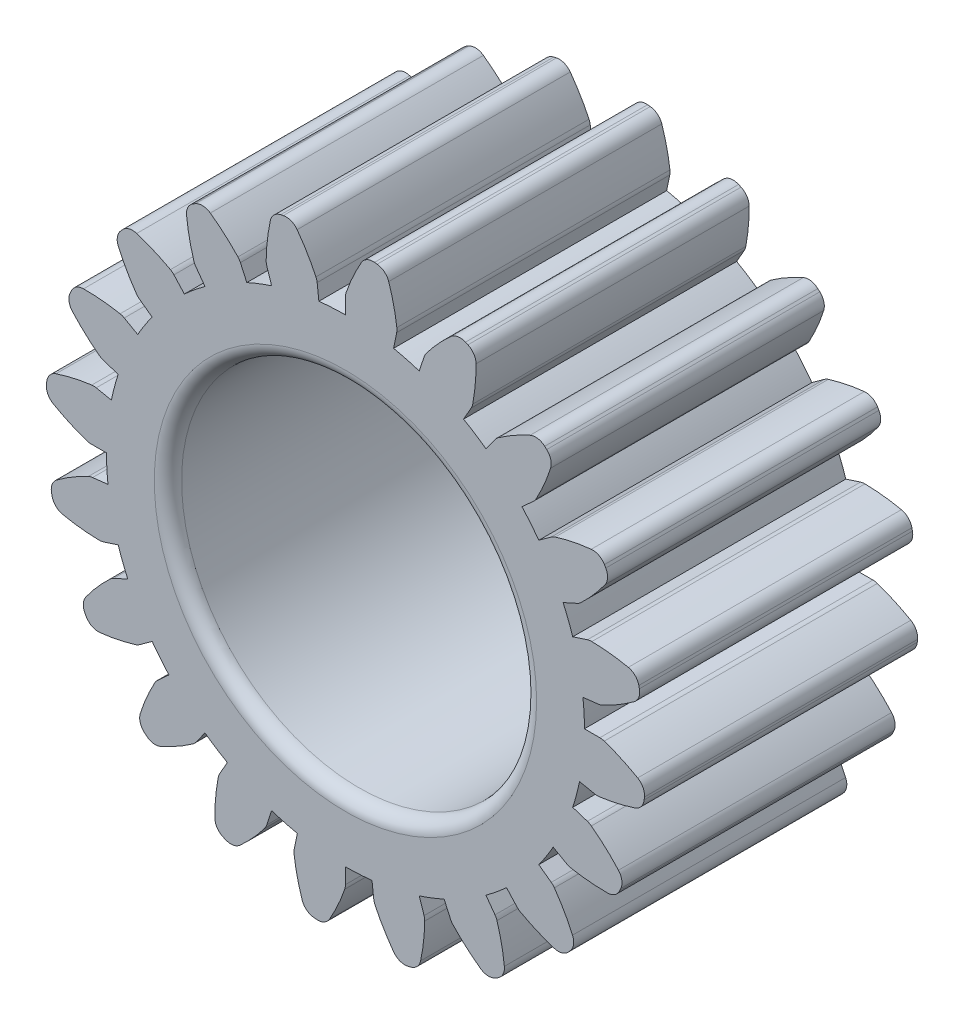
SolidWorks part; units mm, degrees
ref_plane "Front Plane" through (0, 0, 0) normal (1, 0, 0) x (0, 1, 0)
ref_plane "Top Plane" through (0, 0, 0) normal (0, 0, 1) x (0, 1, 0)
ref_plane "Right Plane" through (0, 0, 0) normal (0, 1, 0) x (-1, 0, 0)
sketch "Sketch1" plane through (0, 0, 0) normal (0, 0, 1) x (0, 1, 0)
  line L1 (0, 0) -> (0, 9.3969) construction
  line L2 (0, 0) -> (3.596, 8.6816) construction
  line L3 (0, 0) -> (6.6446, 6.6446) construction
  line L4 (0, 0) -> (8.6816, 3.596) construction
  line L5 (0, 0) -> (9.3969, 0) construction
  line L6 (3.596, 8.6816) -> (0.1868, 10.0938) construction
  line L8 (6.6446, 6.6446) -> (1.4259, 11.8633) construction
  line L9 (8.6816, 3.596) -> (4.4451, 13.8238) construction
  line L11 (9.3969, 0) -> (9.3969, 14.7607) construction
  line L12 (0, 0) -> (1.0119, 9.9487) construction
  line L14 (1.892, 9.2045) -> (0, 0) construction
  line L17 (0, 9.3969) -> (0, 8.75)
  line L18 (1.892, 9.2045) -> (1.7618, 8.5708)
  line L19 (0.2282, 9.9974) -> (0, 0) construction
  circle A16 centre (0, 0) radius 9.3969 construction
  arc A17 (1.4758, 10.9005) -> (0.7492, 10.9745) centre (0, 0) ccw
  circle A18 centre (0, 0) radius 8.75
  arc A19 (0, 10) -> (2.0135, 9.7952) centre (0, 0) ccw construction
  arc A20 (0, 10) -> (2.0135, 9.7952) centre (0, 0) cw
  arc A21 (0, 9.3969) -> (4.4451, 13.8238) centre (6.5729, 7.2422) cw construction
  arc A22 (1.892, 9.2045) -> (-1.5707, 14.4357) centre (-4.9801, 8.4173) ccw construction
  arc A23 (0, 9.3969) -> (0.7492, 10.9745) centre (6.5729, 7.2422) cw
  arc A24 (1.4758, 10.9005) -> (1.892, 9.2045) centre (-4.9801, 8.4173) cw
  circle A25 centre (0, 0) radius 6.5
  point P12 (0, 0)
  dimension "BaseCircle" = 18.7939
  dimension "AddendumCircle" = 22
  dimension "RootCircle" = 17.5
  dimension "PitchCircle" = 20
  dimension "D6" = 13
  dimension "D2" = 14.7607
  dimension "D3" = 11.0705
  dimension "D4" = 7.3803
  dimension "D5" = 3.6902
  dimension "D7" = 4.5
  dimension "D1" = 5
sketch "Sketch2" plane through (0, 0, 0) normal (0, 0, 1) x (0, 1, 0)
  line L8 (1.892, 9.2045) -> (1.7618, 8.5708) construction
  line L9 (0, 9.3969) -> (0, 8.75) construction
  line L10 (1.892, 9.2045) -> (1.7618, 8.5708)
  line L11 (0, 9.3969) -> (0, 8.75)
  arc A0 (1.4758, 10.9005) -> (0.7492, 10.9745) centre (0, 0) ccw construction
  arc A1 (1.4758, 10.9005) -> (0.7492, 10.9745) centre (0, 0) ccw
  arc A7 (0.7492, 10.9745) -> (0, 9.3969) centre (6.5729, 7.2422) ccw construction
  arc A8 (0.7492, 10.9745) -> (0, 9.3969) centre (6.5729, 7.2422) ccw
  arc A9 (1.892, 9.2045) -> (1.4758, 10.9005) centre (-4.9801, 8.4173) ccw construction
  arc A10 (1.892, 9.2045) -> (1.4758, 10.9005) centre (-4.9801, 8.4173) ccw
  circle A12 centre (0, 0) radius 8.75 construction
  arc A13 (1.7618, 8.5708) -> (0, 8.75) centre (0, 0) ccw
extrude "Boss-Extrude5" add sketch "Sketch1" along normal blind 10 contours A18 A19 A20 region at (-8.4589, 0.8604, 0)
extrude "Boss-Extrude6" add sketch "Sketch2" along normal blind 10
fillet "Fillet3" radius 0.5 4 edges at (-10.9005, 1.4758, 5) (-10.9745, 0.7492, 5) (-9.3969, 0, 5) (-9.2045, 1.892, 5)
pattern_circular "CirPattern5" count 20 over 360 about axis through (0, 0, 10) along (0, 0, -1) of "Boss-Extrude6", "Fillet3"
fillet "Fillet2" radius 0.5 1 edges at (6.5, 0, 10)
equation "\"PlanetTeeth\" = 20"
equation "\"Module\" = 1"
equation "\"PressureAngle\" = 20deg"
equation "\"PitchDiameter\"= \"PlanetTeeth\" * \"Module\""
equation "\"OutsideDiameter\"= (\"PlanetTeeth\" + 2) * \"Module\""
equation "\"WholeDepthDia\"= (\"PlanetTeeth\" - 2.5) * \"Module\""
equation "\"BaseCircleDia\"= \"PitchDiameter\" * cos(\"PressureAngle\")"
equation "\"Addendum\"= 1 * \"Module\""
equation "\"Dedendum\"= 1.25 * \"Module\""
equation "\"WholeDepth\"= 2.25 * \"Module\""
equation "\"CircularPitch\"= 360 / \"PlanetTeeth\""
equation "\"FilletRadius\"= \"Module\" / 2"
equation "\"PitchArcLength\"= ( \"CircularPitch\" / 180 * 3.14 * \"BaseCircleDia\" / 2 )"
equation "\"BaseCircle@Sketch1\" = \"BaseCircleDia\""
equation "\"AddendumCircle@Sketch1\"= \"PitchCircle@Sketch1\" + \"Addendum\" * 2"
equation "\"RootCircle@Sketch1\"=\"PitchCircle@Sketch1\" - \"Dedendum\" * 2"
equation "\"PitchCircle@Sketch1\" = \"Module\" * \"PlanetTeeth\""
equation "\"InvoluteArrayMaxLength\"= \"BaseCircleDia\" * pi / 4"
equation "\"D2@Sketch1\"=\"InvoluteArrayMaxLength\""
equation "\"D3@Sketch1\"=\"InvoluteArrayMaxLength\"*3/4"
equation "\"D4@Sketch1\"=\"InvoluteArrayMaxLength\"*2/4"
equation "\"D5@Sketch1\"=\"InvoluteArrayMaxLength\"*1/4"
equation "\"GearWidth\"=10"
equation "\"BearingDiameter\" = 13"
equation "\"D6@Sketch1\" = IIF ( \"PitchCircle@Sketch1\" > \"BearingDiameter\" , \"BearingDiameter\" , \"PitchCircle@Sketch1\" - 3 )"
equation "\"D1@CirPattern5\"=\"PlanetTeeth\""
equation "\"D1@Boss-Extrude6\"=\"GearWidth\""
equation "\"D7@Sketch1\"=\"CircularPitch\"/4"
equation "\"D1@Fillet3\"=\"FilletRadius\""
